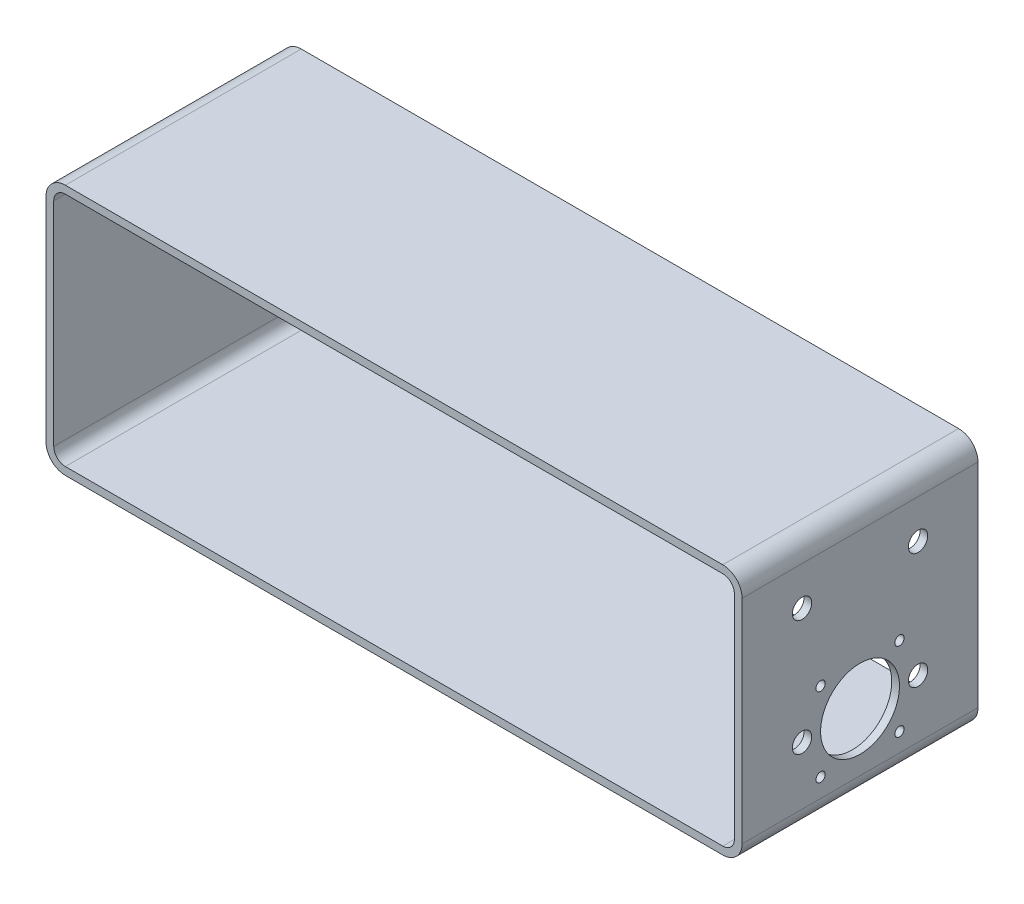
SolidWorks part; units mm, degrees
ref_plane "Front Plane" through (0, 0, 0) normal (0, 0, 1) x (1, 0, 0)
ref_plane "Top Plane" through (0, 0, 0) normal (0, 1, 0) x (1, 0, 0)
ref_plane "Right Plane" through (0, 0, 0) normal (1, 0, 0) x (0, 0, -1)
sketch "Sketch3" plane through (0, 0, 0) normal (0, 0, 1) x (1, 0, 0)
  line L0 (-15.875, 5.7326) -> (15.875, 5.7326) construction
  line L1 (107.95, -41.275) -> (-107.95, -41.275)
  line L2 (114.3, -34.925) -> (114.3, 34.925)
  line L3 (107.95, 41.275) -> (-107.95, 41.275)
  line L4 (-114.3, -34.925) -> (-114.3, 34.925)
  line L5 (114.3, -41.275) -> (-114.3, 41.275) construction
  line L6 (114.3, 41.275) -> (-114.3, -41.275) construction
  line L12 (72.898, 12.7) -> (72.898, -12.7) construction
  line L13 (72.898, -12.7) -> (98.298, -12.7) construction
  line L14 (98.298, -12.7) -> (98.298, 12.7) construction
  line L15 (98.298, 12.7) -> (72.898, 12.7) construction
  line L16 (72.898, 12.7) -> (98.298, -12.7) construction
  line L17 (98.298, 12.7) -> (72.898, -12.7) construction
  line L18 (-98.298, 12.7) -> (-72.898, 12.7) construction
  line L19 (-72.898, 12.7) -> (-72.898, -12.7) construction
  line L20 (-72.898, -12.7) -> (-98.298, -12.7) construction
  line L21 (-98.298, -12.7) -> (-98.298, 12.7) construction
  line L22 (-98.298, 12.7) -> (-72.898, -12.7) construction
  line L23 (-72.898, 12.7) -> (-98.298, -12.7) construction
  line L24 (-15.875, -5.7326) -> (15.875, 5.7326) construction
  line L25 (-15.875, 5.7326) -> (15.875, -5.7326) construction
  line L26 (15.875, 5.7326) -> (15.875, -5.7326) construction
  line L27 (15.875, -5.7326) -> (-15.875, -5.7326) construction
  line L28 (-15.875, -5.7326) -> (-15.875, 5.7326) construction
  line L29 (-15.875, 5.7326) -> (15.875, -5.7326) construction
  line L30 (15.875, 5.7326) -> (-15.875, -5.7326) construction
  arc A0 (114.3, 34.925) -> (107.95, 41.275) centre (107.95, 34.925) ccw
  arc A1 (107.95, -41.275) -> (114.3, -34.925) centre (107.95, -34.925) ccw
  arc A2 (-107.95, -41.275) -> (-114.3, -34.925) centre (-107.95, -34.925) cw
  arc A3 (-107.95, 41.275) -> (-114.3, 34.925) centre (-107.95, 34.925) ccw
  circle A8 centre (-107.95, 34.925) radius 3.175
  circle A9 centre (-107.95, -34.925) radius 3.175
  circle A10 centre (107.95, -34.925) radius 3.175
  circle A11 centre (107.95, 34.925) radius 3.175
  circle A24 centre (-85.598, 0) radius 3.429
  circle A25 centre (85.598, 0) radius 3.429
  circle A26 centre (-15.875, 5.7326) radius 3.175
  circle A27 centre (15.875, 5.7326) radius 3.175
  circle A28 centre (15.875, -5.7326) radius 3.175
  circle A29 centre (-15.875, -5.7326) radius 3.175
  point P0 (0, 0)
  point P22 (-114.3, 0)
  point P23 (0, 0)
  point P57 (-98.298, 0)
  dimension "D3" = 6.35
  dimension "D6" = 16.002
  dimension "D7" = 6.35
  dimension "D8" = 16.002
  dimension "D9" = 28.575
  dimension "D10" = 31.75
  dimension "D11" = 6.35
  dimension "D14" = 25.4
  dimension "D4" = 6.858
  dimension "D5" = 6.858
  dimension "D1" = 82.55
  dimension "D2" = 228.6
  dimension "D12" = 25.4
extrude "Boss-Extrude1" add sketch "Sketch3" along normal blind 77.47
sketch "Sketch4" plane through (0, 0, 77.47) normal (0, 0, 1) x (1, 0, 0)
  line L0 (107.95, 38.735) -> (-107.95, 38.735)
  line L1 (-111.76, 34.925) -> (-111.76, -34.925)
  line L2 (-107.95, -38.735) -> (107.95, -38.735)
  line L3 (111.76, -34.925) -> (111.76, 34.925)
  line L4 (107.95, 41.275) -> (-107.95, 41.275)
  line L5 (-114.3, 34.925) -> (-114.3, -34.925)
  line L6 (-107.95, -41.275) -> (107.95, -41.275)
  line L7 (114.3, -34.925) -> (114.3, 34.925)
  line L8 (107.95, 41.275) -> (-107.95, 41.275)
  line L9 (-114.3, 34.925) -> (-114.3, -34.925)
  line L10 (-107.95, -41.275) -> (107.95, -41.275)
  line L11 (114.3, -34.925) -> (114.3, 34.925)
  arc A0 (111.76, 34.925) -> (107.95, 38.735) centre (107.95, 34.925) ccw
  arc A1 (-107.95, 38.735) -> (-111.76, 34.925) centre (-107.95, 34.925) ccw
  arc A2 (-111.76, -34.925) -> (-107.95, -38.735) centre (-107.95, -34.925) ccw
  arc A3 (107.95, -38.735) -> (111.76, -34.925) centre (107.95, -34.925) ccw
  arc A4 (114.3, 34.925) -> (107.95, 41.275) centre (107.95, 34.925) ccw
  arc A5 (-107.95, 41.275) -> (-114.3, 34.925) centre (-107.95, 34.925) ccw
  arc A6 (-114.3, -34.925) -> (-107.95, -41.275) centre (-107.95, -34.925) ccw
  arc A7 (107.95, -41.275) -> (114.3, -34.925) centre (107.95, -34.925) ccw
  arc A8 (114.3, 34.925) -> (107.95, 41.275) centre (107.95, 34.925) ccw
  arc A9 (-107.95, 41.275) -> (-114.3, 34.925) centre (-107.95, 34.925) ccw
  arc A10 (-114.3, -34.925) -> (-107.95, -41.275) centre (-107.95, -34.925) ccw
  arc A11 (107.95, -41.275) -> (114.3, -34.925) centre (107.95, -34.925) ccw
  circle M19 centre (-85.598, 0) radius 3.429
  circle M28 centre (85.598, 0) radius 3.429
  circle M39 centre (15.875, -5.7326) radius 3.175
  circle M40 centre (-15.875, 5.7326) radius 3.175
  circle M41 centre (15.875, 5.7326) radius 3.175
  circle M42 centre (-15.875, -5.7326) radius 3.175
  dimension "D1" = 0
  dimension "D2" = 2.54
extrude "Cut-Extrude1" cut sketch "Sketch4" against normal through all both and the other way through all contours L3 L0 L1 L2 M39 M19 M28 M42 M41 M40 region at (0, 0, 77.47)
sketch "Sketch6" plane through (114.3, 0, 0) normal (1, 0, 0) x (0, 0, -1)
  line L0 (-57.785, 22.225) -> (-57.785, -15.875) construction
  line L1 (-57.785, -15.875) -> (-19.685, -15.875) construction
  line L2 (-19.685, -15.875) -> (-19.685, 22.225) construction
  line L3 (-19.685, 22.225) -> (-57.785, 22.225) construction
  line L4 (-57.785, 22.225) -> (-19.685, -15.875) construction
  line L5 (-19.685, 22.225) -> (-57.785, -15.875) construction
  line L6 (-77.47, 34.925) -> (0, 34.925) construction
  line L7 (-51.689, -2.921) -> (-51.689, -28.829) construction
  line L8 (-51.689, -28.829) -> (-25.781, -28.829) construction
  line L9 (-25.781, -28.829) -> (-25.781, -2.921) construction
  line L10 (-25.781, -2.921) -> (-51.689, -2.921) construction
  line L11 (-51.689, -2.921) -> (-25.781, -28.829) construction
  line L12 (-25.781, -2.921) -> (-51.689, -28.829) construction
  circle A0 centre (-57.785, 22.225) radius 3.175
  circle A1 centre (-19.685, 22.225) radius 3.175
  circle A2 centre (-19.685, -15.875) radius 3.175
  circle A3 centre (-57.785, -15.875) radius 3.175
  circle A5 centre (-51.689, -2.921) radius 1.524
  circle A6 centre (-25.781, -2.921) radius 1.524
  circle A7 centre (-25.781, -28.829) radius 1.524
  circle A8 centre (-51.689, -28.829) radius 1.524
  circle A9 centre (-38.735, -15.875) radius 12.954
  point P10 (-38.735, 34.925)
  point P11 (-38.735, 3.175)
  point P23 (-38.735, -15.875)
  dimension "D1" = 6.35
  dimension "D5" = 3.048
  dimension "D6" = 25.908
  dimension "D10" = 25.908
  dimension "D2" = 38.1
  dimension "D3" = 38.1
  dimension "D4" = 12.7
  dimension "D7" = 25.908
  dimension "D8" = 25.908
  dimension "D9" = 19.05
extrude "Cut-Extrude3" cut sketch "Sketch6" against normal blind 15.24
